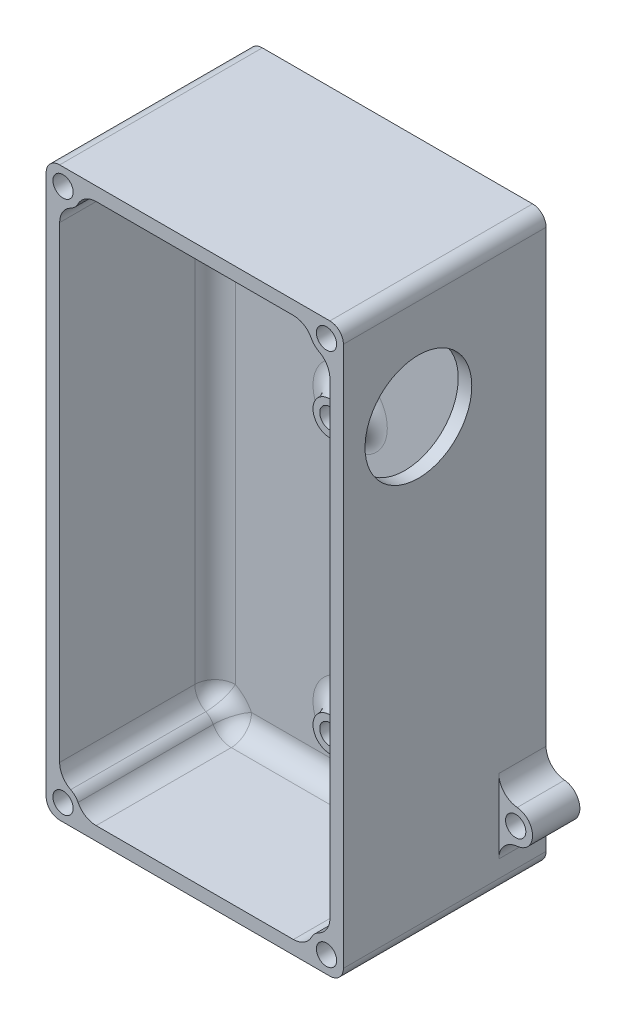
SolidWorks part; units mm, degrees
ref_plane "Front Plane" through (0, 0, 0) normal (0, 0, 1) x (1, 0, 0)
ref_plane "Top Plane" through (0, 0, 0) normal (0, 1, 0) x (1, 0, 0)
ref_plane "Right Plane" through (0, 0, 0) normal (1, 0, 0) x (0, 0, -1)
sketch "Sketch3" plane through (0, 0, 0) normal (0, 0, 1) x (1, 0, 0)
  line L0 (-4.5, 69.5) -> (-2, 69.5)
  line L1 (2.9495, 80) -> (37.0505, 80)
  line L2 (0, 77.0505) -> (0, 2.9495)
  line L3 (2.9495, 0) -> (37.0505, 0)
  line L4 (40, 77.0505) -> (40, 2.9495)
  line L5 (0, 82) -> (40, 82)
  line L6 (-2, 80) -> (-2, 0)
  line L7 (0, -2) -> (40, -2)
  line L8 (42, 80) -> (42, 0)
  line L9 (-4.5, 74.5) -> (-2, 74.5)
  line L10 (44.5, 10.5) -> (42, 10.5)
  line L11 (44.5, 5.5) -> (42, 5.5)
  line L12 (42, 10.5) -> (42, 5.5)
  line L13 (-2, 74.5) -> (-2, 69.5)
  circle A0 centre (20, 9) radius 1.5
  circle A1 centre (20, 49.5) radius 1.5
  circle A2 centre (20, 49.5) radius 2.5
  circle A3 centre (20, 9) radius 2.5
  arc A4 (40, -2) -> (42, 0) centre (40, 0) ccw
  arc A6 (0, 2) -> (0.0018, 1.9149) centre (2, 2) ccw
  arc A7 (-2, 0) -> (0, -2) centre (0, 0) ccw
  arc A9 (0, 82) -> (-2, 80) centre (0, 80) ccw
  arc A11 (40, 82) -> (42, 80) centre (40, 80) cw
  circle A12 centre (0.5, 0.5) radius 1.5
  arc A14 (1.9149, 0.0018) -> (2, 0) centre (2, 2) ccw
  arc A15 (2.9495, 0) -> (0, 2.9495) centre (0.5, 0.5) ccw
  circle A16 centre (39.5, 0.5) radius 1.5
  arc A17 (40, 2.9495) -> (37.0505, 0) centre (39.5, 0.5) ccw
  circle A18 centre (39.5, 79.5) radius 1.5
  arc A19 (37.0505, 80) -> (40, 77.0505) centre (39.5, 79.5) ccw
  circle A20 centre (0.5, 79.5) radius 1.5
  arc A21 (0, 77.0505) -> (2.9495, 80) centre (0.5, 79.5) ccw
  circle A22 centre (44.5, 8) radius 1.5
  circle A23 centre (-4.5, 72) radius 1.5
  arc A24 (44.5, 5.5) -> (44.5, 10.5) centre (44.5, 8) ccw
  arc A25 (-4.5, 74.5) -> (-4.5, 69.5) centre (-4.5, 72) ccw
  point P22 (0, 0)
  point P27 (0, 80)
  point P32 (40, 80)
  dimension "D3" = 20
  dimension "D5" = 3
  dimension "D10" = 3
  dimension "D12" = 5
  dimension "D13" = 2
  dimension "D1" = 80
  dimension "D2" = 40
  dimension "D4" = 9
  dimension "D6" = 2
  dimension "D7" = 2
  dimension "D8" = 2
  dimension "D9" = 2
  dimension "D11" = 40.5
  dimension "D14" = 10
  dimension "D15" = 10
extrude "base" add sketch "Sketch3" along normal blind 7 contours L4 L1 L2 L3 A3 A2 | L8 L5 L6 L7 L1 L4 L3 L2 | A3 A0 | A0 | A2 A1 | A1 | A12 | A16 | A20 | A18 | L13 L0 A25 L9 | L12 L11 A24 L10 | A22 | A23 region at (-1.0517, 72, 0) region at (20, 40.1349, 0) region at (20, 9, 0) region at (20, 49.5, 0) region at (17.5707, 49.5, 0) region at (17.5707, 9, 0) region at (0.5, 0.5, 0) region at (39.5, 0.5, 0) region at (39.5, 79.5, 0) region at (0.5, 79.5, 0)
extrude "walls" add sketch "Sketch3<3>" along normal blind 23 from surface contours L8 L5 L6 L7 L1 L4 L3 L2 region at (-1.0517, 72, 0) starting at face at (20, 40, 7)
sketch "Sketch3<3>" plane through (0, 0, 0) normal (0, 0, 1) x (1, 0, 0) same geometry as "Sketch3"
extrude "standoffs" add sketch "Sketch3<4>" along normal blind 3 from surface contours A2 A1 | A3 A0 region at (17.5707, 49.5, 0) region at (17.5707, 9, 0) starting at face at (20, 40, 7)
sketch "Sketch3<4>" plane through (0, 0, 0) normal (0, 0, 1) x (1, 0, 0) same geometry as "Sketch3"
fillet "Internal Fillet" radius 3 18 edges at (22.5, 9, 7) (22.5, 49.5, 7) (37.7322, 77.7322, 7) (20, 80, 7) (2.2678, 77.7322, 7) (0, 40, 7) (2.2678, 2.2678, 7) (37.7322, 2.2678, 7) (20, 0, 7) (40, 40, 7) (2.9495, 0, 18.5) (0, 2.9495, 18.5) (0, 77.0505, 18.5) (2.9495, 80, 18.5) (37.0505, 0, 18.5) (40, 2.9495, 18.5) (37.0505, 80, 18.5) (40, 77.0505, 18.5)
fillet "External Fillet" radius 3 4 edges at (42, 5.5, 3.5) (42, 10.5, 3.5) (-2, 74.5, 3.5) (-2, 69.5, 3.5)
sketch "Sketch5" plane through (40, 0, 0) normal (-1, 0, 0) x (0, 0, 1)
  line L5 (30, 5.399) -> (30, 74.601) construction
  circle A0 centre (18.9, 65.1682) radius 7.9
  dimension "gland_hole" = 15.8
  dimension "D2" = 11.1
extrude "Cut-Extrude1" cut sketch "Sketch5" against normal blind 10
equation "\"gland_hole\"=9.64661"
equation "\"D2@Sketch5\"=\"gland_hole@Sketch5\"/2+3.2mm"
